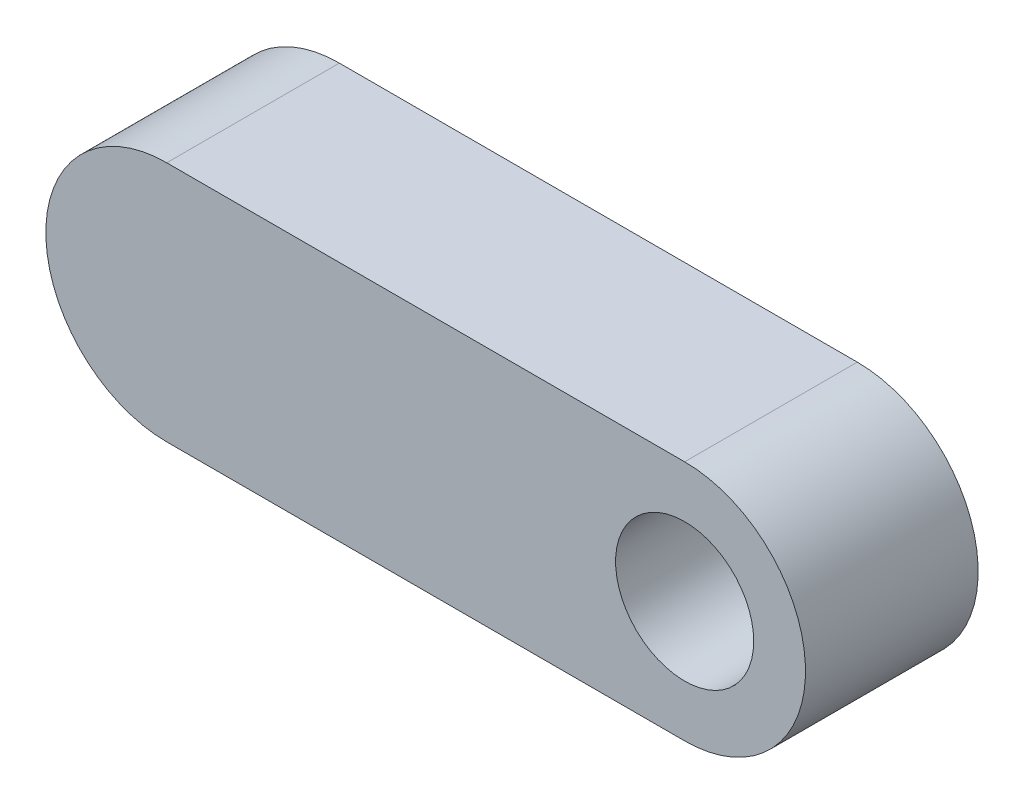
SolidWorks part; units mm, degrees
ref_plane "Płaszczyzna przednia" through (0, 0, 0) normal (0, 0, 1) x (1, 0, 0)
ref_plane "Płaszczyzna górna" through (0, 0, 0) normal (0, 1, 0) x (1, 0, 0)
ref_plane "Płaszczyzna prawa" through (0, 0, 0) normal (1, 0, 0) x (0, 0, -1)
sketch "Szkic1" plane through (0, 0, 0) normal (0, 0, 1) x (1, 0, 0)
  line L0 (0, 0) -> (300, 0) construction
  line L1 (0, 70) -> (300, 70)
  line L2 (0, -70) -> (300, -70)
  arc A0 (0, 70) -> (0, -70) centre (0, 0) ccw
  arc A1 (300, -70) -> (300, 70) centre (300, 0) ccw
  point P3 (150, 0)
  dimension "D1" = 70
  dimension "D2" = 300
extrude "Dodanie-wyciągnięcie1" add sketch "Szkic1" along normal blind 100
sketch "Szkic2" plane through (0, 0, 100) normal (0, 0, 1) x (1, 0, 0)
  circle A0 centre (300, 0) radius 40
  dimension "D1" = 80
extrude "Wytnij-wyciągnięcie1" cut sketch "Szkic2" against normal through all
sketch "Szkic3" plane through (0, 0, 100) normal (0, 0, 1) x (1, 0, 0)
  circle A0 centre (0, 0) radius 19.3863
ref_axis "Oś2" through (0, 0, -135.9106) along (0, 0, 1)
ref_axis "Oś3" through (300, 0, -290.7218) along (0, 0, 1)
sketch "Szkic4" plane through (0, 0, 0) normal (0, 1, 0) x (1, 0, 0)
  line L0 (0, 135.9106) -> (0, -252.3728) construction
  line L3 (0, 0) -> (-70, 0) construction
  point P0 (0, -50)
  point P1 (-87.455, 56.4676)
  dimension "D1" = 50
